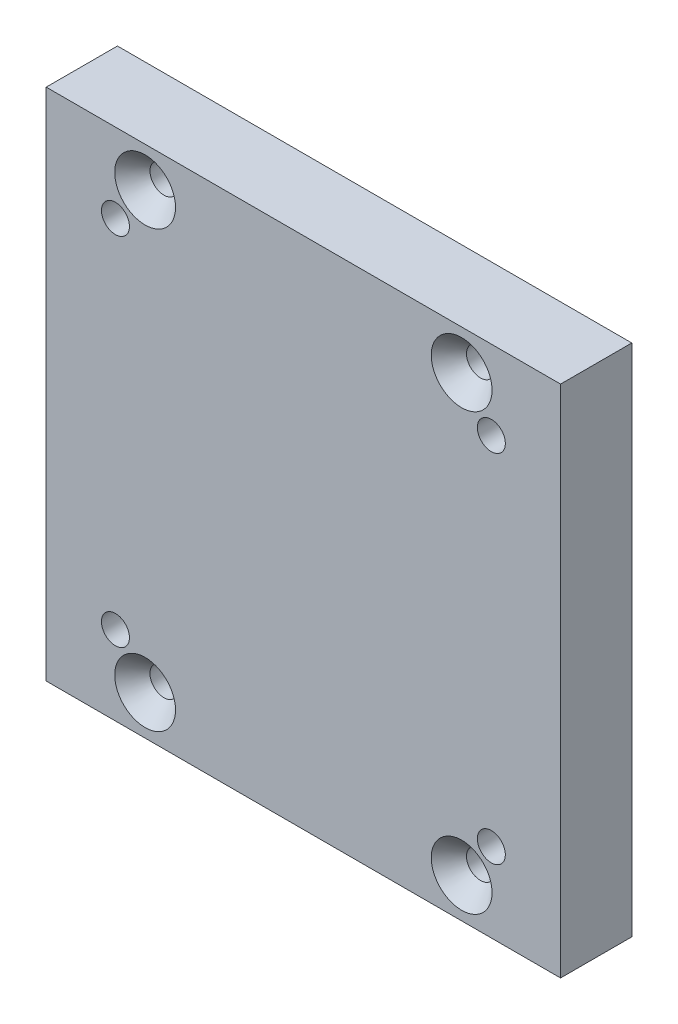
SolidWorks part; units mm, degrees
material "6061-T6 (SS)"
ref_plane "Front Plane" through (0, 0, 0) normal (0, 0, 1) x (1, 0, 0)
ref_plane "Top Plane" through (0, 0, 0) normal (0, 1, 0) x (1, 0, 0)
ref_plane "Right Plane" through (0, 0, 0) normal (1, 0, 0) x (0, 0, -1)
sketch "Sketch1" plane through (0, 0, 0) normal (0, 0, 1) x (1, 0, 0)
  line L0 (-38.1, 0) -> (0, 0) construction
  line L1 (0, 0) -> (-30.48, 30.48) construction
  line L3 (41.275, -41.275) -> (-41.275, -41.275)
  line L4 (41.275, -41.275) -> (41.275, 41.275)
  line L5 (41.275, 41.275) -> (-41.275, 41.275)
  line L6 (-41.275, -41.275) -> (-41.275, 41.275)
  line L7 (41.275, -41.275) -> (-41.275, 41.275) construction
  line L8 (41.275, 41.275) -> (-41.275, -41.275) construction
  circle A0 centre (0, 0) radius 38.1 construction
  circle A1 centre (-30.48, 30.48) radius 2.5527 construction
  dimension "D1" = 76.2
  dimension "D2" = 5.1054
  dimension "D4" = 82.55
  dimension "D3" = 45
  dimension "D5" = 30.48
extrude "Boss-Extrude1" add sketch "Sketch1" along normal blind 11.43
sketch "Sketch2" plane through (0, 0, 0) normal (0, 0, -1) x (-1, 0, 0)
  circle A0 centre (0, 0) radius 38.1
  dimension "D1" = 76.2
extrude "Cut-Extrude1" cut sketch "Sketch2" against normal blind 8.89
hole_wizard "CSK for #8 Flat Head Machine Screw1" positions "Sketch4" profile "Sketch3" countersink size "#8" standard "ANSI Inch" end condition through all
sketch "Sketch4" plane through (0, 0, 11.43) normal (0, 0, 1) x (1, 0, 0)
  line L0 (-25.4, 34.925) -> (25.4, -34.925) construction
  line L3 (25.4, 34.925) -> (-25.4, -34.925) construction
  point P0 (25.4, 34.925)
  point P1 (-25.4, 34.925)
  point P3 (-25.4, -34.925)
  point P5 (25.4, -34.925)
  dimension "D1" = 50.8
  dimension "D2" = 69.85
sketch "Sketch3" plane through (25.4, 34.925, 11.43) normal (1, 0, 0) x (0, -1, 0)
  line L0 (0, 0) -> (0, 11.43)
  line L1 (0, 11.43) -> (2.2479, 11.43)
  line L2 (2.2479, 11.43) -> (2.2479, 3.0265)
  line L3 (2.2479, 3.0265) -> (4.8788, 0)
  line L5 (4.8788, 0) -> (0, 0)
  line L6 (-2.2479, 3.0265) -> (-4.8788, 0) construction
  line L11 (0, -6.35) -> (0, 107.95) construction
  dimension "Thru Hole Dia." = 4.4958
  dimension "Thru Hole Depth" = 11.43
  dimension "Near C'Sink Dia." = 9.7576
  dimension "Near C'Sink Angle" = 82
hole_wizard "#8 Clearance Hole1" positions "Sketch7" profile "Sketch6" hole size "#8" standard "ANSI Inch" end condition through all
sketch "Sketch7" plane through (0, 0, 11.43) normal (0, 0, 1) x (1, 0, 0)
  line L1 (-30.1625, 28.575) -> (30.1625, 28.575)
  line L2 (-30.1625, 28.575) -> (-30.1625, -28.575)
  line L3 (-30.1625, -28.575) -> (30.1625, -28.575)
  line L4 (30.1625, 28.575) -> (30.1625, -28.575)
  line L5 (-30.1625, 28.575) -> (30.1625, -28.575) construction
  line L6 (-30.1625, -28.575) -> (30.1625, 28.575) construction
  point P2 (30.1625, -28.575)
  point P49 (-30.1625, 28.575)
  point P50 (-30.1625, -28.575)
  point P51 (30.1625, 28.575)
  dimension "D1" = 60.325
  dimension "D2" = 57.15
sketch "Sketch6" plane through (30.1625, -28.575, 11.43) normal (1, 0, 0) x (0, -1, 0)
  line L0 (0, 0) -> (0, 11.43)
  line L1 (0, 11.43) -> (2.2479, 11.43)
  line L2 (2.2479, 11.43) -> (2.2479, 0)
  line L5 (2.2479, 0) -> (0, 0)
  line L11 (0, -6.35) -> (0, 107.95) construction
  dimension "Thru Hole Dia." = 4.4958
  dimension "Thru Hole Depth" = 11.43
